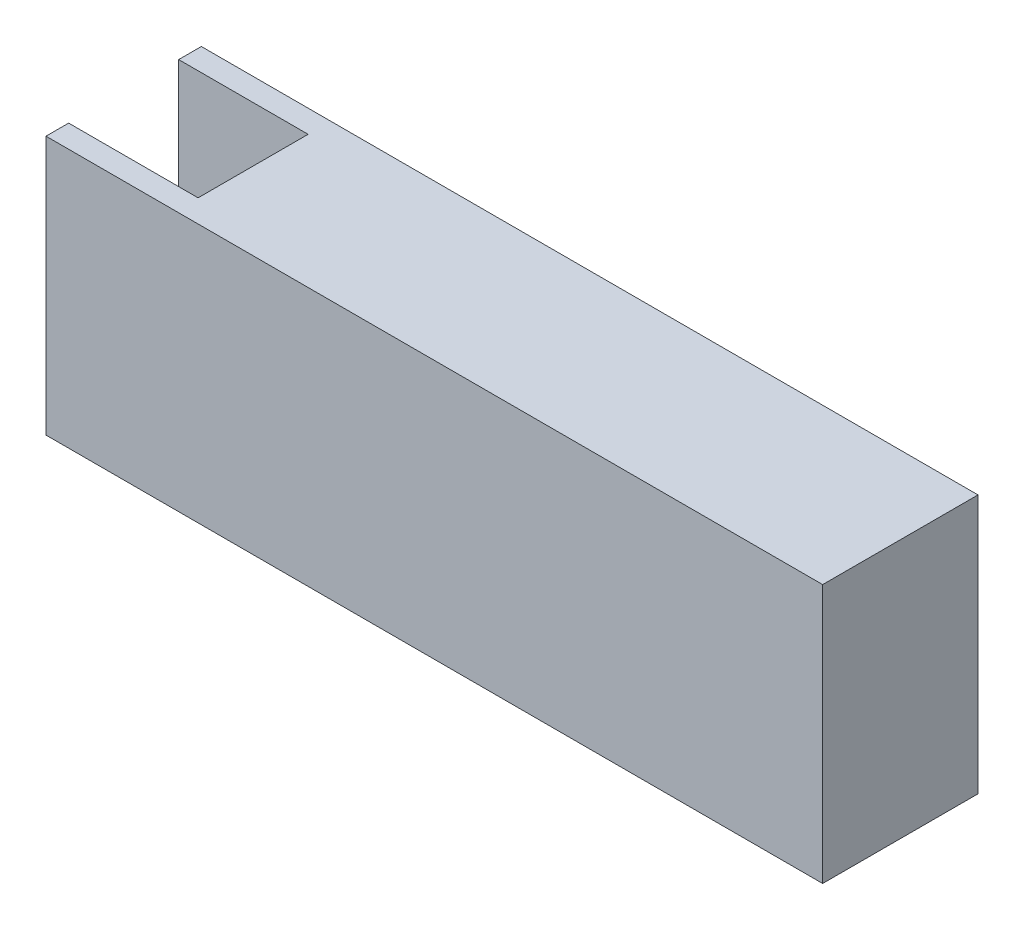
SolidWorks part; units mm, degrees
note: The reader was unsure of these and kept them because the rebuilt part matched: shared geometry of "Sketch1<4>".
ref_plane "Front Plane" through (0, 0, 0) normal (0, 0, 1) x (1, 0, 0)
ref_plane "Top Plane" through (0, 0, 0) normal (0, 1, 0) x (1, 0, 0)
ref_plane "Right Plane" through (0, 0, 0) normal (1, 0, 0) x (0, 0, -1)
sketch "Sketch1" plane through (0, 0, 0) normal (0, 1, 0) x (1, 0, 0)
  line L0 (-128.7859, 0) -> (4, 0) construction
  line L1 (-1, 3) -> (29, 3)
  line L2 (29, 3) -> (29, -3)
  line L3 (29, -3) -> (-1, -3)
  line L4 (-1, -3) -> (-1, 3)
  line L5 (-1, -2.125) -> (29, -2.125)
  line L6 (29, 2.125) -> (-1, 2.125)
  line L8 (4, 2.125) -> (4, -2.125)
  line L9 (5, 0) -> (6310.5096, 0) construction
  dimension "D1" = 6
  dimension "D2" = 30
  dimension "D3" = 5
  dimension "D4" = 4.25
extrude "Boss-Extrude1" add sketch "Sketch1" along normal blind 10
extrude "Cut-Extrude1" cut sketch "Sketch1<4>" along normal through all contours L8 L6 L4 L5
sketch "Sketch1<4>" plane through (0, 0, 0) normal (0, 1, 0) x (1, 0, 0) same geometry as "Sketch1"
